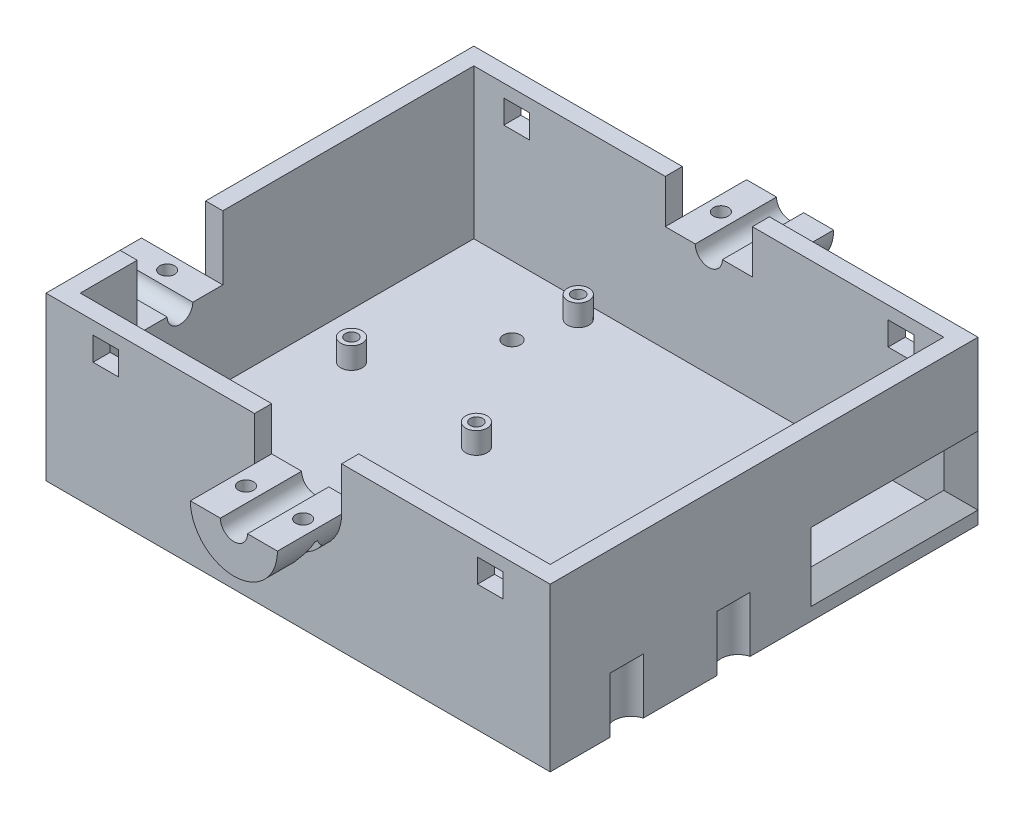
SolidWorks part; units mm, degrees
ref_plane "Front Plane" through (0, 0, 0) normal (0, 0, 1) x (1, 0, 0)
ref_plane "Top Plane" through (0, 0, 0) normal (0, 1, 0) x (1, 0, 0)
ref_plane "Right Plane" through (0, 0, 0) normal (1, 0, 0) x (0, 0, -1)
sketch "Sketch1" plane through (0, 0, 0) normal (0, 1, 0) x (1, 0, 0)
  line L0 (0, 0) -> (0, 100)
  line L1 (0, 0) -> (117.85, 0)
  line L2 (117.85, 0) -> (117.85, 100)
  line L3 (0, 100) -> (117.85, 100)
  dimension "D1" = 100
  dimension "D2" = 117.85
extrude "Boss-Extrude1" add sketch "Sketch1" along normal blind 3
sketch "Sketch2" plane through (0, 3, 0) normal (0, 1, 0) x (1, 0, 0)
  line L4 (117.85, 100) -> (0, 100) construction
  line L5 (117.85, 0) -> (117.85, 100) construction
  line L12 (12, 24.65) -> (112.85, 24.65) construction
  line L13 (112.85, 24.65) -> (112.85, 95) construction
  line L14 (112.85, 95) -> (12, 95) construction
  line L15 (12, 95) -> (12, 24.65) construction
  circle A0 centre (32.45, 91.96) radius 2.5
  circle A1 centre (94.6, 91.73) radius 2.5
  circle A2 centre (14.59, 56.81) radius 2.5
  circle A3 centre (46.39, 54.22) radius 2.5
  circle A4 centre (110.27, 27.32) radius 2.5
  circle A5 centre (32.45, 91.96) radius 1.45
  circle A6 centre (14.59, 56.81) radius 1.45
  circle A7 centre (46.39, 54.22) radius 1.45
  circle A8 centre (94.6, 91.73) radius 1.45
  circle A9 centre (110.27, 27.32) radius 1.45
  dimension "D4" = 5
  dimension "D5" = 2.9
  dimension "D12" = 2.67
  dimension "D2" = 67.31
  dimension "D3" = 20.45
  dimension "D6" = 67.08
  dimension "D7" = 82.6
  dimension "D8" = 2.59
  dimension "D9" = 32.16
  dimension "D10" = 29.57
  dimension "D11" = 34.39
  dimension "D13" = 98.27
  dimension "D14" = 5
  dimension "D15" = 70.35
  dimension "D16" = 100.85
  dimension "D17" = 5
extrude "Boss-Extrude2" add sketch "Sketch2" along normal blind 5
sketch "Sketch3" plane through (0, 3, 0) normal (0, 1, 0) x (1, 0, 0)
  line L0 (117.85, 0) -> (117.85, 100) construction
  line L1 (0, 0) -> (117.85, 0) construction
  line L2 (0, 100) -> (0, 0) construction
  line L3 (117.85, 100) -> (0, 100) construction
  line L4 (117.85, 0) -> (117.85, 100)
  line L5 (0, 0) -> (117.85, 0)
  line L6 (0, 100) -> (0, 0)
  line L7 (117.85, 100) -> (0, 100)
  line L18 (113.85, 96) -> (4, 96)
  line L19 (4, 96) -> (4, 4)
  line L20 (4, 4) -> (113.85, 4)
  line L21 (113.85, 4) -> (113.85, 96)
  dimension "D1" = 4
extrude "Boss-Extrude3" add sketch "Sketch3" along normal offset from surface (35 mm away) 30 up to face at (32.45, 8, -89.46) offset beyond the face yes
sketch "Sketch4" plane through (0, 8, 0) normal (0, 1, 0) x (1, 0, 0)
  line L0 (117.85, 100) -> (113.85, 96)
  line L1 (117.85, 66) -> (113.85, 66)
  line L2 (117.85, 0) -> (117.85, 100) construction
  line L4 (113.85, 66) -> (113.85, 96)
  line L5 (117.85, 100) -> (117.85, 66)
  dimension "D1" = 30
extrude "Cut-Extrude1" cut sketch "Sketch4" along normal blind 6
chamfer "Chamfer1" distance 5 angle 45 3 edges at (117.85, 8, -83) (117.85, 14, -83) (117.85, 11, -66)
sketch "Sketch6" plane through (0, 0, -100) normal (0, 0, -1) x (-1, 0, 0)
  line L0 (-117.85, 38) -> (0, 38) construction
  line L1 (-58.925, 0) -> (-58.925, 14.18) construction
  line L2 (-117.85, 0) -> (0, 0) construction
  line L3 (-69.1, 27.825) -> (-69.1, 38)
  line L4 (-48.75, 27.825) -> (-48.75, 38)
  line L5 (-69.1, 38) -> (-48.75, 38)
  arc A0 (-69.1, 27.825) -> (-48.75, 27.825) centre (-58.925, 27.825) ccw
  circle A1 centre (-58.925, 27.825) radius 3.175
  dimension "D1" = 6.35
  dimension "D2" = 7
extrude "Boss-Extrude4" add sketch "Sketch6" along normal blind 15 contours A1 | L4 L5 L3 A0 region at (58.925, 27.825, -100)
sketch "Sketch7" plane through (0, 0, -115) normal (0, 0, -1) x (-1, 0, 0)
  line L0 (-62.1, 27.825) -> (-69.1, 27.825)
  line L1 (-69.1, 27.825) -> (-69.1, 38)
  line L2 (-117.85, 38) -> (-69.1, 38) construction
  line L3 (-69.1, 38) -> (-48.75, 38) construction
  line L4 (-69.1, 38) -> (-48.75, 38)
  line L5 (-48.75, 38) -> (-48.75, 27.825)
  line L6 (-48.75, 27.825) -> (-55.75, 27.825)
  circle A0 centre (-58.925, 27.825) radius 3.175
  circle A1 centre (-58.925, 27.825) radius 3.175 construction
  line M3 (-48.75, 27.825) -> (-48.75, 38)
  line M4 (-48.75, 38) -> (-69.1, 38)
  line M5 (-69.1, 38) -> (-69.1, 27.825)
  circle M6 centre (-58.925, 27.825) radius 3.175
extrude "Cut-Extrude2" cut sketch "Sketch7" against normal up to surface (19 mm away) contours L6 L0 M3 M4 M5 M6 | M6 region at (58.925, 33.2222, -115) region at (58.925, 27.825, -115) up to face at (77.2333, 17.3333, -96)
sketch "Sketch8" plane through (0, 0, -115) normal (0, 0, -1) x (-1, 0, 0)
  line L0 (-58.925, 24.65) -> (-58.925, 17.65) construction
  circle A0 centre (-58.925, 21.15) radius 1.75
  arc A1 (-62.1, 27.825) -> (-55.75, 27.825) centre (-58.925, 27.825) ccw construction
  arc A2 (-69.1, 27.825) -> (-48.75, 27.825) centre (-58.925, 27.825) ccw construction
  dimension "D1" = 3.5
extrude "Cut-Extrude3" cut sketch "Sketch8" against normal blind 5
fillet "Fillet1" radius 1 1 edges at (57.175, 21.15, -115)
sketch "Sketch9" plane through (0, 27.825, 0) normal (0, 1, 0) x (1, 0, 0)
  line L0 (48.75, 115) -> (55.75, 115) construction
  line L1 (58.925, 115) -> (58.925, 102.2564) construction
  line L2 (62.1, 115) -> (55.75, 115) construction
  line L3 (52.25, 115) -> (52.25, 96) construction
  line L4 (65.6, 115) -> (65.6, 96) construction
  line L5 (62.1, 115) -> (69.1, 115) construction
  line L6 (113.85, 96) -> (4, 96) construction
  line L7 (62.1, 96) -> (69.1, 96) construction
  circle A0 centre (52.25, 105.5) radius 1.75
  circle A1 centre (65.6, 105.5) radius 1.75
  dimension "D1" = 3.5
extrude "Cut-Extrude4" cut sketch "Sketch9" against normal through all
ref_plane "Plane1" through (0, 24.825, 0) normal (0, 1, 0) x (1, 0, 0)
sketch "Sketch10" plane through (0, 24.825, 0) normal (0, 1, 0) x (1, 0, 0)
  line L1 (55.4832, 105.5) -> (53.8666, 108.3)
  line L2 (53.8666, 108.3) -> (50.6334, 108.3)
  line L3 (50.6334, 108.3) -> (49.0168, 105.5)
  line L4 (49.0168, 105.5) -> (50.6334, 102.7)
  line L5 (50.6334, 102.7) -> (53.8666, 102.7)
  line L6 (53.8666, 102.7) -> (55.4832, 105.5)
  line L7 (68.8332, 105.5) -> (67.2166, 108.3)
  line L8 (67.2166, 108.3) -> (63.9834, 108.3)
  line L9 (63.9834, 108.3) -> (62.3668, 105.5)
  line L10 (62.3668, 105.5) -> (63.9834, 102.7)
  line L11 (63.9834, 102.7) -> (67.2166, 102.7)
  line L12 (67.2166, 102.7) -> (68.8332, 105.5)
  circle A0 centre (52.25, 105.5) radius 2.8 construction
  circle A1 centre (65.6, 105.5) radius 2.8 construction
  dimension "D1" = 5.6
extrude "Cut-Extrude5" cut sketch "Sketch10" against normal through all
sketch "Sketch11" plane through (0, 3, 0) normal (0, 1, 0) x (1, 0, 0)
  line L0 (0, 50) -> (117.85, 50) construction
  line L1 (0, 100) -> (0, 0) construction
  line L2 (117.85, 0) -> (117.85, 100) construction
  line L3 (58.925, 0) -> (58.925, 100) construction
  line L4 (0, 0) -> (117.85, 0) construction
  circle A0 centre (28.925, 80) radius 2
  circle A1 centre (88.925, 80) radius 2
  circle A2 centre (28.925, 20) radius 2
  circle A3 centre (88.925, 20) radius 2
  dimension "D5" = 4
  dimension "D1" = 60
  dimension "D2" = 60
  dimension "D3" = 30
  dimension "D4" = 30
extrude "Cut-Extrude6" cut sketch "Sketch11" against normal through all
sketch "Sketch12" plane through (0, 0, 0) normal (-1, 0, 0) x (0, 0, 1)
  line L0 (-27.32, 8) -> (-27.32, 3) construction
  line L1 (-51.72, 8) -> (-56.72, 8) construction
  line L2 (-37.32, 23) -> (-37.32, 38)
  line L3 (-100, 38) -> (0, 38) construction
  line L4 (-37.32, 38) -> (-17.32, 38)
  line L5 (-17.32, 38) -> (-17.32, 23)
  line L6 (-37.32, 38) -> (-17.32, 38)
  circle A0 centre (-27.32, 23) radius 3
  arc A1 (-37.32, 23) -> (-17.32, 23) centre (-27.32, 23) ccw
  line M4 (0, 38) -> (-100, 38)
  dimension "D1" = 6
  dimension "D2" = 7
  dimension "D3" = 15
  dimension "D4" = 0
extrude "Boss-Extrude7" add sketch "Sketch12" along normal blind 15 contours L2 A1 L5 A0 M4 region at (0, 26.6924, -27.32)
sketch "Sketch13" plane through (-15, 0, 0) normal (-1, 0, 0) x (0, 0, 1)
  line L0 (-30.32, 23) -> (-37.32, 23)
  line L1 (-37.32, 23) -> (-37.32, 38)
  line L2 (-37.32, 38) -> (-17.32, 38)
  line L3 (-17.32, 38) -> (-17.32, 23)
  line L4 (-17.32, 23) -> (-24.32, 23)
  circle A0 centre (-27.32, 23) radius 3
  circle A1 centre (-27.32, 23) radius 3 construction
  circle M1 centre (-27.32, 23) radius 3
  line M2 (-37.32, 38) -> (-37.32, 23)
  line M4 (-17.32, 23) -> (-17.32, 38)
  line M5 (-17.32, 38) -> (-37.32, 38)
extrude "Cut-Extrude7" cut sketch "Sketch13" against normal up to surface (19 mm away) contours L4 L0 M4 M5 M2 M1 | M1 region at (-15, 30.8079, -27.32) region at (-15, 23, -27.32) up to face at (4, 20.5, -50)
sketch "Sketch14" plane through (0, 23, 0) normal (0, 1, 0) x (1, 0, 0)
  line L0 (-15, 33.82) -> (4, 33.82) construction
  line L1 (-15, 30.32) -> (-15, 37.32) construction
  line L2 (4, 96) -> (4, 4) construction
  line L3 (-15, 20.82) -> (4, 20.82) construction
  line L4 (-15, 17.32) -> (-15, 24.32) construction
  line L5 (4, 17.32) -> (4, 24.32) construction
  circle A0 centre (-5.5, 33.82) radius 1.75
  circle A1 centre (-5.5, 20.82) radius 1.75
  dimension "D1" = 3.5
extrude "Cut-Extrude8" cut sketch "Sketch14" against normal through all
ref_plane "Plane2" through (0, 20, 0) normal (0, 1, 0) x (1, 0, 0)
sketch "Sketch15" plane through (0, 20, 0) normal (0, 1, 0) x (1, 0, 0)
  line L1 (-2.7, 32.2034) -> (-2.7, 35.4366)
  line L2 (-2.7, 35.4366) -> (-5.5, 37.0532)
  line L3 (-5.5, 37.0532) -> (-8.3, 35.4366)
  line L4 (-8.3, 35.4366) -> (-8.3, 32.2034)
  line L5 (-8.3, 32.2034) -> (-5.5, 30.5868)
  line L6 (-5.5, 30.5868) -> (-2.7, 32.2034)
  line L7 (-5.5, 24.0532) -> (-8.3, 22.4366)
  line L8 (-8.3, 22.4366) -> (-8.3, 19.2034)
  line L9 (-8.3, 19.2034) -> (-5.5, 17.5868)
  line L10 (-5.5, 17.5868) -> (-2.7, 19.2034)
  line L11 (-2.7, 19.2034) -> (-2.7, 22.4366)
  line L12 (-2.7, 22.4366) -> (-5.5, 24.0532)
  circle A0 centre (-5.5, 33.82) radius 2.8 construction
  circle A1 centre (-5.5, 20.82) radius 2.8 construction
  dimension "D1" = 5.6
extrude "Cut-Extrude9" cut sketch "Sketch15" against normal blind 15
ref_plane "Plane3" through (0, 0, -50) normal (0, 0, 1) x (1, 0, 0)
mirror "Mirror1" about plane through (0, 0, -50) normal (0, 0, 1) of "Cut-Extrude5", "Cut-Extrude4", "Boss-Extrude4"
sketch "Sketch16" plane through (0, 0, 15) normal (0, 0, 1) x (1, 0, 0)
  line L0 (55.75, 27.825) -> (48.75, 27.825)
  line L1 (48.75, 27.825) -> (48.75, 38)
  line L2 (48.75, 38) -> (69.1, 38)
  line L3 (69.1, 38) -> (69.1, 27.825)
  line L4 (62.1, 27.825) -> (69.1, 27.825)
  circle A0 centre (58.925, 27.825) radius 3.175 construction
  circle A1 centre (58.925, 27.825) radius 3.175 construction
  circle A2 centre (58.925, 27.825) radius 3.175
  circle M2 centre (58.925, 27.825) radius 3.175
  line M4 (69.1, 27.825) -> (69.1, 38)
  line M5 (69.1, 38) -> (48.75, 38)
  line M6 (48.75, 38) -> (48.75, 27.825)
extrude "Cut-Extrude10" cut sketch "Sketch16" against normal up to surface (19 mm away) contours L4 L0 M2 M4 M5 M6 | M2 region at (58.925, 33.2222, 15) region at (58.925, 27.825, 15) up to face at (58.925, 20.5, -4)
sketch "Sketch17" plane through (0, 0, -96) normal (0, 0, 1) x (1, 0, 0)
  line L0 (0, 38) -> (48.75, 38) construction
  line L1 (11, 35) -> (17, 35)
  line L2 (11, 35) -> (11, 29.5)
  line L3 (11, 29.5) -> (17, 29.5)
  line L4 (17, 35) -> (17, 29.5)
  line L5 (100.85, 35) -> (106.85, 35)
  line L6 (100.85, 35) -> (100.85, 29.5)
  line L7 (100.85, 29.5) -> (106.85, 29.5)
  line L8 (106.85, 35) -> (106.85, 29.5)
  line L9 (0, 38) -> (0, 0) construction
  line L11 (117.85, 38) -> (117.85, 0) construction
  dimension "D1" = 5.5
  dimension "D2" = 3
  dimension "D3" = 6
  dimension "D4" = 11
  dimension "D5" = 6
  dimension "D6" = 5.5
  dimension "D7" = 11
extrude "Cut-Extrude11" cut sketch "Sketch17" against normal through all both and the other way through all
sketch "Sketch18" plane through (0, 0, 0) normal (0, -1, 0) x (1, 0, 0)
  circle A0 centre (118.885, -42.8954) radius 4
  circle A1 centre (118.885, -17.8954) radius 4
  dimension "D2" = 8
  dimension "D1" = 25
  dimension "D3" = 57.1046
  dimension "D4" = 1.035
extrude "Cut-Extrude12" cut sketch "Sketch18" against normal blind 13
